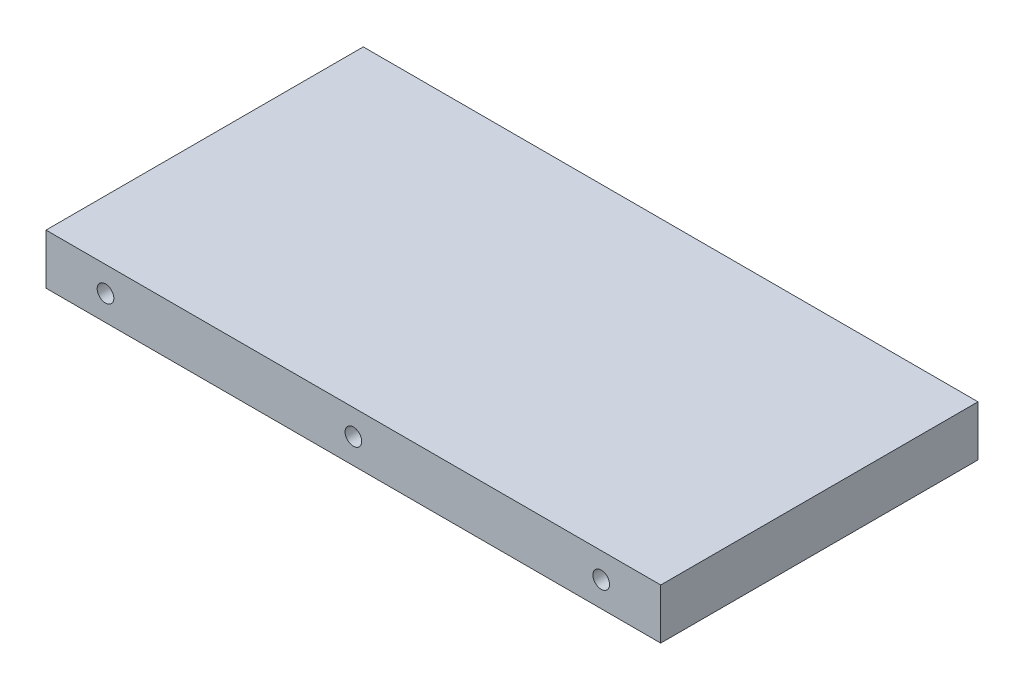
SolidWorks part; units mm, degrees
ref_plane "Front Plane" through (0, 0, 0) normal (0, 0, 1) x (1, 0, 0)
ref_plane "Top Plane" through (0, 0, 0) normal (0, 1, 0) x (1, 0, 0)
ref_plane "Right Plane" through (0, 0, 0) normal (1, 0, 0) x (0, 0, -1)
ref_axis "Axis1" through (0, 0, -88.99) along (0, 0, 1)
ref_axis "Axis2" through (0, -55, 0) along (0, 1, 0)
ref_axis "Axis3" through (-88.99, 0, 0) along (1, 0, 0)
sketch "Sketch1" plane through (0, 0, 0) normal (0, 1, 0) x (1, 0, 0)
  line L1 (77.5, -40) -> (-77.5, -40)
  line L2 (77.5, -40) -> (77.5, 40)
  line L3 (77.5, 40) -> (-77.5, 40)
  line L4 (-77.5, -40) -> (-77.5, 40)
  line L5 (77.5, -40) -> (-77.5, 40) construction
  line L6 (77.5, 40) -> (-77.5, -40) construction
  point P0 (0, 0)
  dimension "D1" = 80
  dimension "D2" = 155
extrude "Boss-Extrude1" add sketch "Sketch1" along normal blind 12.7
hole_wizard "Tap Drill for M5x0.8 Tap1" positions "Sketch3" profile "Sketch2" hole size "M5x0.8" standard "ANSI Metric" end condition through all
sketch "Sketch3" plane through (0, 0, 40) normal (0, 0, 1) x (1, 0, 0)
  line L0 (-77.5, 6.35) -> (-62.5, 6.35) construction
  line L1 (-77.5, 12.7) -> (-77.5, 0) construction
  line L2 (-62.5, 6.35) -> (0, 6.35) construction
  line L3 (0, 6.35) -> (0, 0) construction
  point P0 (-62.5, 6.35)
  point P2 (0, 6.35)
  point P16 (62.5, 6.35)
  dimension "D1" = 15
sketch "Sketch2" plane through (-62.5, 6.35, 40) normal (1, 0, 0) x (0, -1, 0)
  line L0 (0, 0) -> (0, 80)
  line L1 (0, 80) -> (2.1, 80)
  line L2 (2.1, 80) -> (2.1, 0)
  line L5 (2.1, 0) -> (0, 0)
  line L11 (0, -6.35) -> (0, 107.95) construction
  dimension "Thru Hole Dia." = 4.2
  dimension "Thru Hole Depth" = 80
